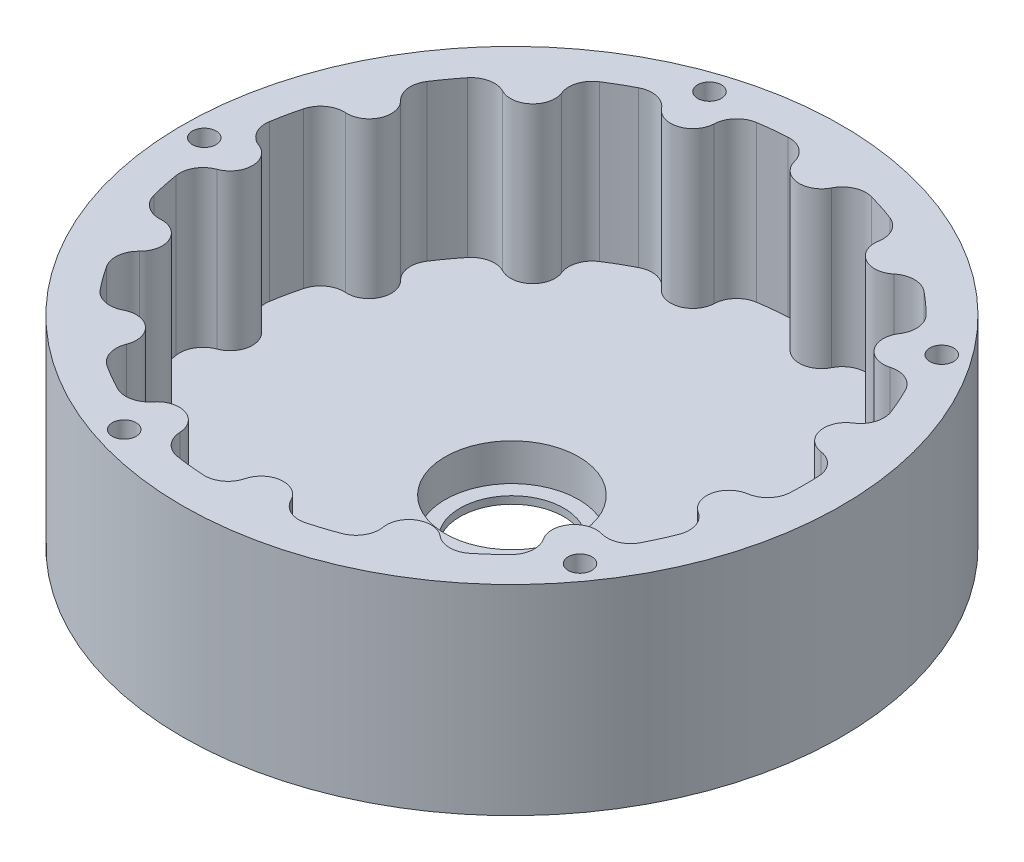
SolidWorks part; units mm, degrees
ref_plane "Front Plane" through (0, 0, 0) normal (0, 0, 1) x (1, 0, 0)
ref_plane "Top Plane" through (0, 0, 0) normal (0, 1, 0) x (1, 0, 0)
ref_plane "Right Plane" through (0, 0, 0) normal (1, 0, 0) x (0, 0, -1)
sketch "Sketch1" plane through (0, 0, 0) normal (0, 1, 0) x (1, 0, 0)
  line L0 (0, 0) -> (-38, 0) construction
  line L1 (-38.6368, 8.2125) -> (0, 0) construction
  circle A0 centre (0, 0) radius 44.45
  arc A1 (-36.9604, -2.8141) -> (-36.9604, 2.8141) centre (-38, 0) ccw
  arc A2 (-36.9604, 2.8141) -> (-38.9946, 6.2987) centre (-35.8602, 5.7924) cw
  arc A3 (-38.9946, 6.2987) -> (-38.6368, 8.2125) centre (0, 0) cw
  arc A4 (-38.9946, -6.2987) -> (-38.6368, -8.2125) centre (0, 0) ccw
  arc A5 (-36.9604, -2.8141) -> (-38.9946, -6.2987) centre (-35.8602, -5.7924) ccw
  arc A6 (-38.1852, 10.1064) -> (-38.6368, 8.2125) centre (0, 0) ccw
  arc A7 (-34.9096, 12.4623) -> (-38.1852, 10.1064) centre (-35.1159, 9.294) ccw
  arc A8 (-34.9096, 12.4623) -> (-32.6204, 17.604) centre (-34.7147, 15.456) ccw
  arc A9 (-32.6204, 17.604) -> (-33.0614, 21.6147) centre (-30.4039, 19.8773) cw
  arc A10 (-33.0614, 21.6147) -> (-31.9562, 23.2175) centre (0, 0) cw
  arc A11 (-30.7733, 24.764) -> (-31.9562, 23.2175) centre (0, 0) ccw
  arc A12 (-26.8226, 25.5839) -> (-30.7733, 24.764) centre (-28.2997, 22.7734) ccw
  arc A13 (-26.8226, 25.5839) -> (-22.64, 29.35) centre (-25.427, 28.2395) ccw
  arc A14 (-22.64, 29.35) -> (-21.4116, 33.1933) centre (-19.6906, 30.5252) cw
  arc A15 (-21.4116, 33.1933) -> (-19.75, 34.208) centre (0, 0) cw
  arc A16 (-18.0404, 35.1396) -> (-19.75, 34.208) centre (0, 0) ccw
  arc A17 (-14.0978, 34.2818) -> (-18.0404, 35.1396) centre (-16.5903, 32.3151) ccw
  arc A18 (-14.0978, 34.2818) -> (-8.745, 36.0211) centre (-11.7426, 36.1401) ccw
  arc A19 (-8.745, 36.0211) -> (-6.0596, 39.0324) centre (-5.5725, 35.895) cw
  arc A20 (-6.0596, 39.0324) -> (-4.1289, 39.2836) centre (0, 0) cw
  arc A21 (-2.1881, 39.4393) -> (-4.1289, 39.2836) centre (0, 0) ccw
  arc A22 (1.0647, 37.0521) -> (-2.1881, 39.4393) centre (-2.0123, 36.2692) ccw
  arc A23 (1.0647, 37.0521) -> (6.6621, 36.4638) centre (3.9721, 37.7918) ccw
  arc A24 (6.6621, 36.4638) -> (10.3402, 38.1226) centre (9.5091, 35.0583) cw
  arc A25 (10.3402, 38.1226) -> (12.2062, 37.5667) centre (0, 0) cw
  arc A26 (14.0425, 36.9196) -> (12.2062, 37.5667) centre (0, 0) ccw
  arc A27 (16.0431, 33.4157) -> (14.0425, 36.9196) centre (12.9137, 33.952) ccw
  arc A28 (16.0431, 33.4157) -> (20.9173, 30.6016) centre (19, 32.909) ccw
  arc A29 (20.9173, 30.6016) -> (24.9521, 30.6209) centre (22.9465, 28.1596) cw
  arc A30 (24.9521, 30.6209) -> (26.4307, 29.3542) centre (0, 0) cw
  arc A31 (27.845, 28.0162) -> (26.4307, 29.3542) centre (0, 0) ccw
  arc A32 (28.2475, 24.0015) -> (27.845, 28.0162) centre (25.6068, 25.7642) ccw
  arc A33 (28.2475, 24.0015) -> (31.5557, 19.4481) centre (30.7426, 22.3358) ccw
  arc A34 (31.5557, 19.4481) -> (35.2495, 17.8247) centre (32.4162, 16.3919) cw
  arc A35 (35.2495, 17.8247) -> (36.085, 16.0661) centre (0, 0) cw
  arc A36 (36.8329, 14.2685) -> (36.085, 16.0661) centre (0, 0) ccw
  arc A37 (35.5677, 10.4371) -> (36.8329, 14.2685) centre (33.8723, 13.1216) ccw
  arc A38 (35.5677, 10.4371) -> (36.7378, 4.9319) centre (37.1696, 7.9006) ccw
  arc A39 (36.7378, 4.9319) -> (39.452, 1.9464) centre (36.2809, 1.7899) cw
  arc A40 (39.452, 1.9464) -> (39.5, 0) centre (0, 0) cw
  arc A41 (39.452, -1.9464) -> (39.5, 0) centre (0, 0) ccw
  arc A42 (36.7378, -4.9319) -> (39.452, -1.9464) centre (36.2809, -1.7899) ccw
  arc A43 (36.7378, -4.9319) -> (35.5677, -10.4371) centre (37.1696, -7.9006) ccw
  arc A44 (35.5677, -10.4371) -> (36.8329, -14.2685) centre (33.8723, -13.1216) cw
  arc A45 (36.8329, -14.2685) -> (36.085, -16.0661) centre (0, 0) cw
  arc A46 (35.2495, -17.8247) -> (36.085, -16.0661) centre (0, 0) ccw
  arc A47 (31.5557, -19.4481) -> (35.2495, -17.8247) centre (32.4162, -16.3919) ccw
  arc A48 (31.5557, -19.4481) -> (28.2475, -24.0015) centre (30.7426, -22.3358) ccw
  arc A49 (28.2475, -24.0015) -> (27.845, -28.0162) centre (25.6068, -25.7642) cw
  arc A50 (27.845, -28.0162) -> (26.4307, -29.3542) centre (0, 0) cw
  arc A51 (24.9521, -30.6209) -> (26.4307, -29.3542) centre (0, 0) ccw
  arc A52 (20.9173, -30.6016) -> (24.9521, -30.6209) centre (22.9465, -28.1596) ccw
  arc A53 (20.9173, -30.6016) -> (16.0431, -33.4157) centre (19, -32.909) ccw
  arc A54 (16.0431, -33.4157) -> (14.0425, -36.9196) centre (12.9137, -33.952) cw
  arc A55 (14.0425, -36.9196) -> (12.2062, -37.5667) centre (0, 0) cw
  arc A56 (10.3402, -38.1226) -> (12.2062, -37.5667) centre (0, 0) ccw
  arc A57 (6.6621, -36.4638) -> (10.3402, -38.1226) centre (9.5091, -35.0583) ccw
  arc A58 (6.6621, -36.4638) -> (1.0647, -37.0521) centre (3.9721, -37.7918) ccw
  arc A59 (1.0647, -37.0521) -> (-2.1881, -39.4393) centre (-2.0123, -36.2692) cw
  arc A60 (-2.1881, -39.4393) -> (-4.1289, -39.2836) centre (0, 0) cw
  arc A61 (-6.0596, -39.0324) -> (-4.1289, -39.2836) centre (0, 0) ccw
  arc A62 (-8.745, -36.0211) -> (-6.0596, -39.0324) centre (-5.5725, -35.895) ccw
  arc A63 (-8.745, -36.0211) -> (-14.0978, -34.2818) centre (-11.7426, -36.1401) ccw
  arc A64 (-14.0978, -34.2818) -> (-18.0404, -35.1396) centre (-16.5903, -32.3151) cw
  arc A65 (-18.0404, -35.1396) -> (-19.75, -34.208) centre (0, 0) cw
  arc A66 (-21.4116, -33.1933) -> (-19.75, -34.208) centre (0, 0) ccw
  arc A67 (-22.64, -29.35) -> (-21.4116, -33.1933) centre (-19.6906, -30.5252) ccw
  arc A68 (-22.64, -29.35) -> (-26.8226, -25.5839) centre (-25.427, -28.2395) ccw
  arc A69 (-26.8226, -25.5839) -> (-30.7733, -24.764) centre (-28.2997, -22.7734) cw
  arc A70 (-30.7733, -24.764) -> (-31.9562, -23.2175) centre (0, 0) cw
  arc A71 (-33.0614, -21.6147) -> (-31.9562, -23.2175) centre (0, 0) ccw
  arc A72 (-32.6204, -17.604) -> (-33.0614, -21.6147) centre (-30.4039, -19.8773) ccw
  arc A73 (-32.6204, -17.604) -> (-34.9096, -12.4623) centre (-34.7147, -15.456) ccw
  arc A74 (-34.9096, -12.4623) -> (-38.1852, -10.1064) centre (-35.1159, -9.294) cw
  arc A75 (-38.1852, -10.1064) -> (-38.6368, -8.2125) centre (0, 0) cw
  dimension "D1" = 88.9
  dimension "D3" = 3
  dimension "D4" = 39.5
  dimension "D5" = 3.175
  dimension "D2" = 38
  dimension "D6" = 12
  dimension "D7" = 15
extrude "Boss-Extrude1" add sketch "Sketch1" along normal blind 27 contours A0 A74 A75 A4 A5 A1 A2 A3 A6 A7 A8 A9 A10 A11 A12 A13 A14 A15 A16 A17 A18 A19 A20 A21 A22 A23 A24 A25 A26 A27 A28 A29 A30 A31 A32 A33 A34 A35 A36 A37 A38 A39 A40 A41 A42 A43 A44 A45 A46 A47 region at (-43.1928, 0, 0)
extrude "Boss-Extrude2" add sketch "Sketch1<3>" along normal blind 6 contours A0 A74 A75 A4 A5 A1 A2 A3 A6 A7 A8 A9 A10 A11 A12 A13 A14 A15 A16 A17 A18 A19 A20 A21 A22 A23 A24 A25 A26 A27 A28 A29 A30 A31 A32 A33 A34 A35 A36 A37 A38 A39 A40 A41 A42 A43 A44 A45 A46 A47 | A75 A74 A73 A72 A71 A70 A69 A68 A67 A66 A65 A64 A63 A62 A61 A60 A59 A58 A57 A56 A55 A54 A53 A52 A51 A50 A49 A48 A47 A46 A45 A44 A43 A42 A41 A40 A39 A38 A37 A36 A35 A34 A33 A32 A31 A30 A29 A28 A27 A26 A25 region at (-43.1928, 0, 0) region at (0, 0, 0)
sketch "Sketch1<3>" plane through (0, 0, 0) normal (0, 1, 0) x (1, 0, 0) same geometry as "Sketch1"
sketch "Sketch2" plane through (0, 0, 0) normal (0, 1, 0) x (1, 0, 0)
  circle A0 centre (0, 0) radius 9
  circle A1 centre (0, 0) radius 7
  dimension "D1" = 18
extrude "Cut-Extrude1" cut sketch "Sketch2" along normal through all contours A1 region at (0, 0, 0)
extrude "Cut-Extrude2" cut sketch "Sketch2<3>" along normal through all from offset 1 contours A0 A1 region at (-8.7454, 0, 0)
sketch "Sketch2<3>" plane through (0, 0, 0) normal (0, 1, 0) x (1, 0, 0) same geometry as "Sketch2"
hole_wizard "M3 Clearance Hole1" positions "Sketch4" profile "Sketch6" hole size "M3" standard "ANSI Metric" end condition through all
sketch "Sketch4" plane through (0, 27, 0) normal (0, 1, 0) x (1, 0, 0)
  line L2 (-41.5, 0) -> (0, 0) construction
  point P10 (-41.5, 0)
  dimension "D1" = 41.5
sketch "Sketch6" plane through (-41.5, 27, 0) normal (1, 0, 0) x (0, 0, 1)
  line L0 (0, 0) -> (0, 27)
  line L1 (0, 27) -> (1.6, 27)
  line L2 (1.6, 27) -> (1.6, 0)
  line L5 (1.6, 0) -> (0, 0)
  line L11 (0, -6.35) -> (0, 107.95) construction
  dimension "Thru Hole Dia." = 3.2
  dimension "Thru Hole Depth" = 27
pattern_circular "CirPattern1" count 5 over 360 about axis through (0, 27, 0) along (0, -1, 0) of "M3 Clearance Hole1" reverse direction yes
equation "\"Ratio\"= 15"
equation "\"Hull Diameter\"= 3.5in"
equation "\"Fixed Ring Diameter\"= 76"
equation "\"Fixed Pin Diameter\"= 6"
equation "\"Output Ring Diameter\"= 40"
equation "\"Output Pin Diameter\"= 6"
equation "\"Disk Bearing Inner Diameter\"= 9"
equation "\"Disk Bearing Outer Diameter\"= 17"
equation "\"Disk Bearing Height\"= 5"
equation "\"Shaft Bearing Inner Diameter\"= 15"
equation "\"Shaft Bearing Outer Diameter\"= 21"
equation "\"Shaft Bearing Height\"= 4"
equation "\"Eccentricity\"= 1.5"
equation "\"Disk Height\"= 8"
equation "\"Disk Spacing\"= 5"
equation "\"Hull Height\"= 40"
equation "\"Shaft End Bearing Inner Diameter\"= 12"
equation "\"Shaft End Bearing Outer Diameter\"= 18"
equation "\"Shaft End Bearing Height\"= 4"
equation "\"Output Bearing Inner Diameter\"= 55"
equation "\"Output Bearing Outer Diameter\"= 72"
equation "\"Outer Bearing Height\"= 9"
equation "\"D1@Sketch1\"=\"Hull Diameter\""
equation "\"D3@Sketch1\"=\"Fixed Pin Diameter\"/2"
equation "\"D2@Sketch1\"=\"Fixed Ring Diameter\"/2"
equation "\"D4@Sketch1\"=(\"Fixed Ring Diameter\"/2)+(\"Eccentricity\")"
equation "\"D6@Sketch1\"=180/(\"Ratio\")"
equation "\"D7@Sketch1\"=\"Ratio\""
equation "\"D1@Sketch2\"=\"Shaft End Bearing Outer Diameter\""
